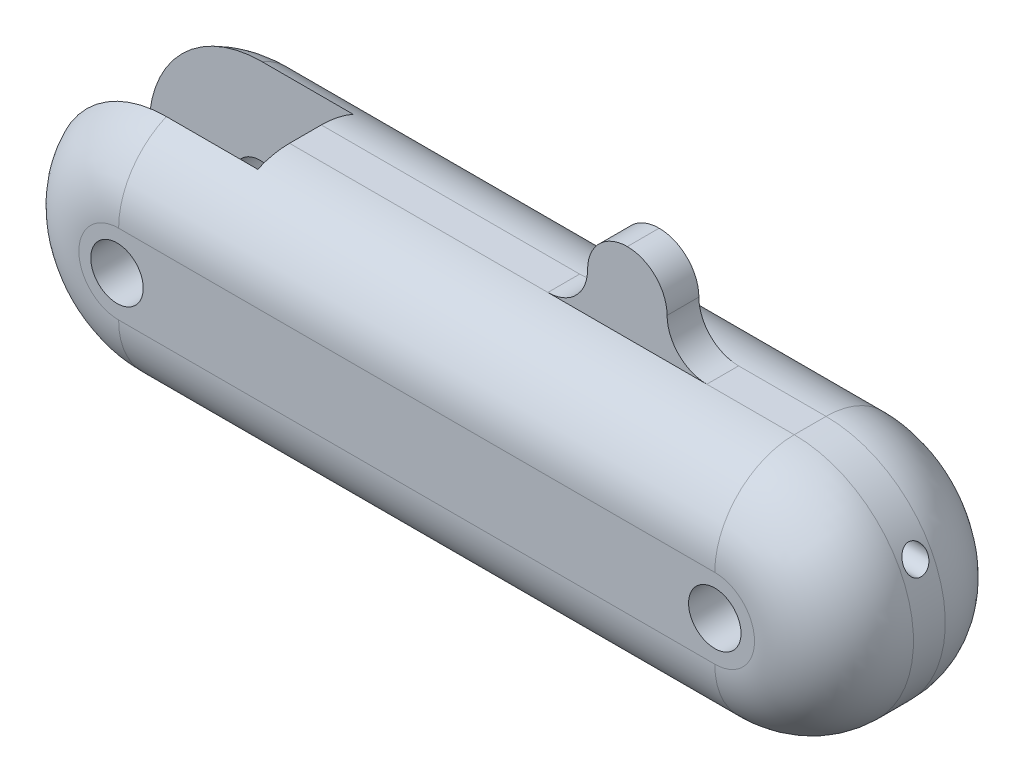
SolidWorks part; units mm, degrees
ref_plane "Front Plane" through (0, 0, 0) normal (0, 0, 1) x (1, 0, 0)
ref_plane "Top Plane" through (0, 0, 0) normal (0, 1, 0) x (1, 0, 0)
ref_plane "Right Plane" through (0, 0, 0) normal (1, 0, 0) x (0, 0, -1)
sketch "Sketch2" plane through (0, 0, 0) normal (0, 0, 1) x (1, 0, 0)
  line L0 (-18.75, 0) -> (18.75, 0)
  line L1 (-18.75, -15) -> (18.75, -15)
  arc A0 (-18.75, 0) -> (-18.75, -15) centre (-18.75, -7.5) ccw
  arc A1 (18.75, 0) -> (18.75, -15) centre (18.75, -7.5) cw
  point P4 (0, 0)
  dimension "D5" = 7.5
  dimension "D1" = 37.5
  dimension "D6" = 37.5
extrude "Boss-Extrude1" add sketch "Sketch2" along normal blind 12
fillet "Fillet1" radius 5 8 edges at (26.25, -7.5, 0) (0, -15, 0) (-26.25, -7.5, 0) (26.25, -7.5, 12) (0, -15, 12) (-26.25, -7.5, 12) (0, 0, 0) (0, 0, 12)
sketch "Sketch3" plane through (0, 0, 12) normal (0, 0, 1) x (1, 0, 0)
  circle A0 centre (-18.8535, -7.5) radius 1.65
  circle A1 centre (18.75, -7.5) radius 1.65
  dimension "D1" = 3.3
  dimension "D3" = 6
  dimension "D4" = 7.5
ref_plane "Plane1" through (11.25, 0, 0) normal (-1, 0, 0) x (0, 0, 1)
ref_plane "Plane3" through (0, -25, 0) normal (0, -1, 0) x (-1, 0, 0)
sketch "Sketch5" plane through (0, -25, 0) normal (0, -1, 0) x (-1, 0, 0)
  line L0 (21.25, 0) -> (18.75, 0) construction
  line L1 (13, -3) -> (26.25, -3)
  line L2 (13, -3) -> (13, -9)
  line L3 (13, -9) -> (26.25, -9)
  line L4 (26.25, -3) -> (26.25, -9)
  line L5 (18.75, -12) -> (-18.75, -12) construction
  line L7 (26.25, -7) -> (26.25, -5) construction
  point P4 (13, -6)
  dimension "D1" = 3
  dimension "D2" = 3
  dimension "D3" = 13
extrude "Cut-Extrude3" cut sketch "Sketch5" against normal through all
sketch "Sketch6" plane through (0, 0, 0) normal (0, 1, 0) x (1, 0, 0)
  line L0 (13.75, -12) -> (13.75, 0) construction
  line L1 (5.75, -5) -> (10.75, -5)
  line L2 (5.75, -5) -> (5.75, -7)
  line L3 (5.75, -7) -> (10.75, -7)
  line L4 (10.75, -5) -> (10.75, -7)
  line L5 (18.75, -7) -> (18.75, -12) construction
  line L6 (18.75, -5) -> (-13, -5) construction
  point P4 (10.75, -6)
  point P7 (13.75, -6)
  dimension "D1" = 5
  dimension "D3" = 8
extrude "Boss-Extrude2" add sketch "Sketch6" along normal blind 5
fillet "Fillet2" radius 2.5 2 edges at (10.75, 5, 6) (5.75, 5, 6)
fillet "Fillet3" radius 2.5 2 edges at (5.75, 0, 6) (10.75, 0, 6)
extrude "Cut-Extrude4" cut sketch "Sketch3" against normal through all
ref_plane "Plane4" through (26.25, 0, 0) normal (1, 0, 0) x (0, 0, -1)
sketch "Sketch8" plane through (26.25, 0, 0) normal (1, 0, 0) x (0, 0, -1)
  line L0 (-7, -15) -> (-5, -15) construction
  circle A0 centre (-6, -4) radius 0.75
  point P6 (-6, -15)
  dimension "D1" = 1.5
  dimension "D2" = 4
extrude "Cut-Extrude7" cut sketch "Sketch8" against normal through all
sketch "Sketch9" plane through (-13, 0, 0) normal (-1, 0, 0) x (0, 0, 1)
  line L1 (7, -15) -> (5, -15) construction
  circle A0 centre (6, -11) radius 0.75
  dimension "D1" = 1.5
  dimension "D2" = 4
sketch "Sketch10" plane through (0, -15, 0) normal (0, -1, 0) x (1, 0, 0)
  line L0 (18.75, 7) -> (18.75, 5) construction
  line L2 (18.75, 12) -> (18.75, 7) construction
  circle A0 centre (12.75, 6) radius 0.75
  point P5 (18.75, 6)
  point P10 (18.75, 9.5)
  dimension "D1" = 1.5
  dimension "D2" = 6
sketch "Sketch11" plane through (0, 0, 12) normal (0, 0, 1) x (1, 0, 0)
  line L0 (-13, -11) -> (12.75, -15) construction
  line L1 (-13, -10.25) -> (-13, -11.75) construction
  line L2 (12, -15) -> (13.5, -15) construction
extrude "Cut-Extrude9" cut sketch "Sketch9" along direction (0.9881, -0.1535, 0) on the side against the normal up to vertex (25.75 mm away) contours A0 up to point (12.75, -15, 6)
